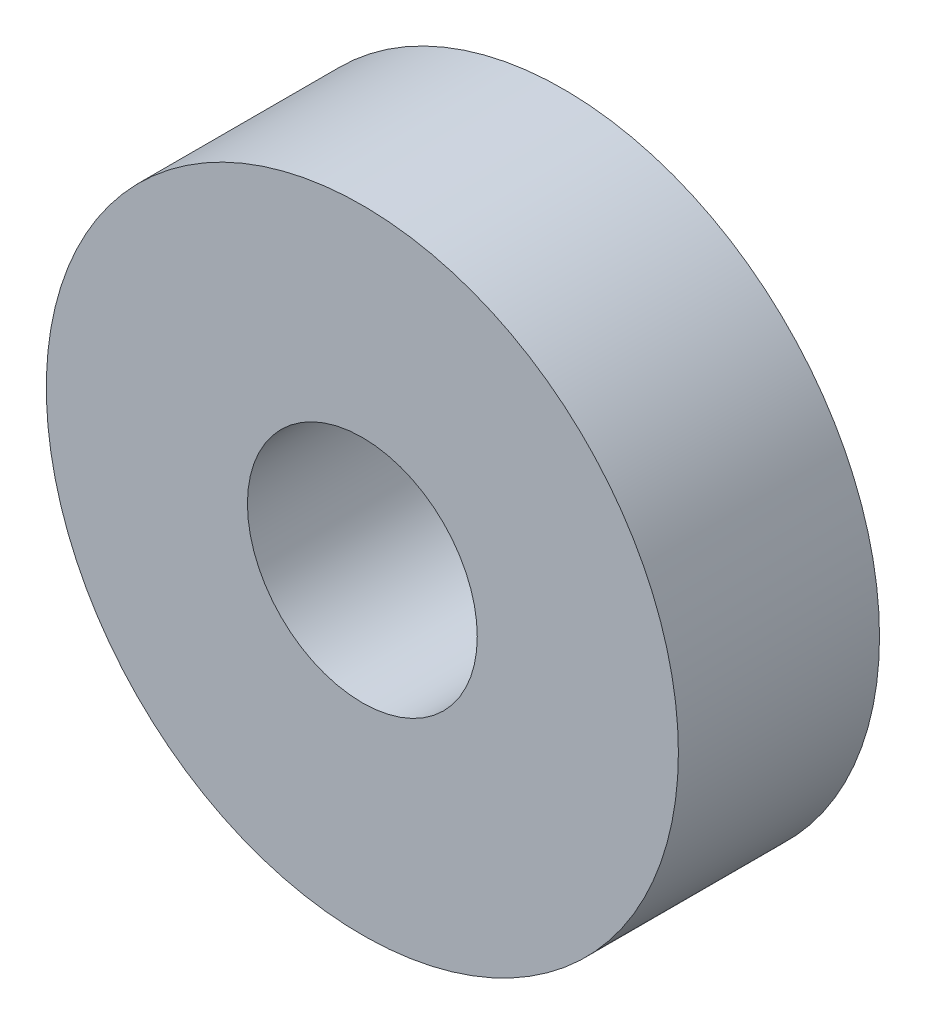
SolidWorks part; units mm, degrees
material "AISI 321 Annealed Stainless Steel (SS)"
ref_plane "Front (1)" through (0, 0, 0) normal (0, 0, 1) x (1, 0, 0)
ref_plane "Top (2)" through (0, 0, 0) normal (0, 1, 0) x (1, 0, 0)
ref_plane "Right (3)" through (0, 0, 0) normal (1, 0, 0) x (0, 0, -1)
ref_axis "X Axis" through (13.5064, 0, 0) along (-1, 0, 0)
ref_axis "Y Axis" through (0, 12.3593, 0) along (0, -1, 0)
ref_axis "Z Axis" through (0, 0, 14.1119) along (0, 0, -1)
sketch "Sketch2" plane through (0, 0, 0) normal (0, 0, 1) x (1, 0, 0)
  circle A0 centre (0, 0) radius 4
  circle A1 centre (0, 0) radius 11
  dimension "D1" = 8
  dimension "D2" = 22
extrude "Boss-Extrude1" add sketch "Sketch2" along normal mid plane 7
